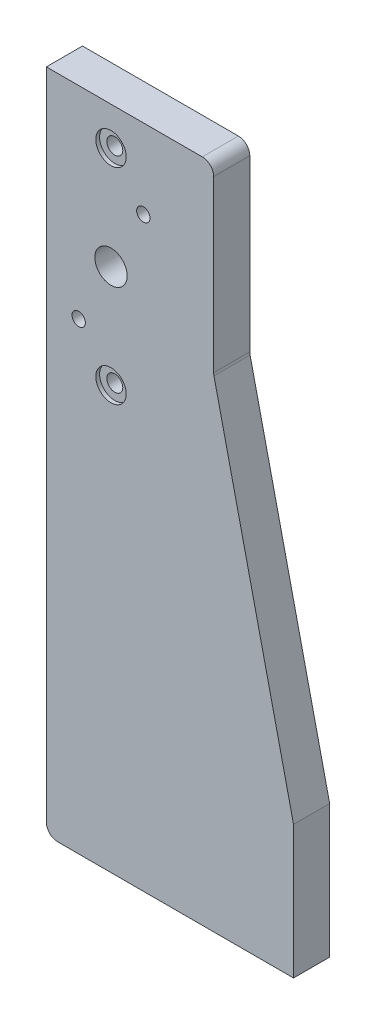
SolidWorks part; units mm, degrees
ref_plane "前视基准面" through (0, 0, 0) normal (0, 0, 1) x (1, 0, 0)
ref_plane "上视基准面" through (0, 0, 0) normal (0, 1, 0) x (1, 0, 0)
ref_plane "右视基准面" through (0, 0, 0) normal (1, 0, 0) x (0, 0, -1)
sketch "草图5" plane through (0, 0, 0) normal (0, 0, 1) x (1, 0, 0)
  line L0 (0, 0) -> (0, 175)
  line L1 (0, 175) -> (44, 175)
  line L2 (44, 175) -> (44, 127)
  line L3 (44, 127) -> (65, 35)
  line L4 (65, 35) -> (65, 0)
  line L5 (65, 0) -> (0, 0)
  line L6 (16, 175) -> (16, 0) construction
  dimension "D1" = 65
  dimension "D2" = 175
  dimension "D3" = 44
  dimension "D4" = 48
  dimension "D5" = 35
  dimension "D6" = 16
extrude "凸台-拉伸1" add sketch "草图5" along normal blind 9.5
sketch "草图6" plane through (0, 0, 9.5) normal (0, 0, 1) x (1, 0, 0)
  line L0 (17, 175) -> (17, 0) construction
  line L1 (44, 175) -> (0, 175) construction
  line L2 (0, 0) -> (65, 0) construction
  line L3 (0, 175) -> (0, 0) construction
  circle A0 centre (17, 165) radius 2.1
  circle A1 centre (17, 111) radius 2.1
  dimension "D2" = 4.2
  dimension "D3" = 10
  dimension "D4" = 54
  dimension "D1" = 17
extrude "切除-拉伸5" cut sketch "草图6" against normal through all contours A1 | A0
sketch "草图7" plane through (0, 0, 9.5) normal (0, 0, 1) x (1, 0, 0)
  circle A0 centre (17, 165) radius 4
  circle A1 centre (17, 111) radius 4
  dimension "D1" = 8
extrude "切除-拉伸6" cut sketch "草图7" against normal blind 1
fillet "圆角1" radius 3 3 edges at (0, 0, 4.75) (44, 127, 4.75) (44, 175, 4.75)
sketch "草图8" plane through (0, 0, 9.5) normal (0, 0, 1) x (1, 0, 0)
  line L0 (17, 165) -> (17, 111) construction
  circle A3 centre (17, 138) radius 4.25
  dimension "D1" = 8.5
extrude "切除-拉伸7" cut sketch "草图8" against normal blind 10
sketch "草图9" plane through (0, 0, 0) normal (0, 0, -1) x (-1, 0, 0)
  circle A0 centre (-25.5, 154.1497) radius 1.75
  circle A1 centre (-8.5, 121.8503) radius 1.75
  dimension "D1" = 3.5
extrude "切除-拉伸8" cut sketch "草图9" against normal through all
